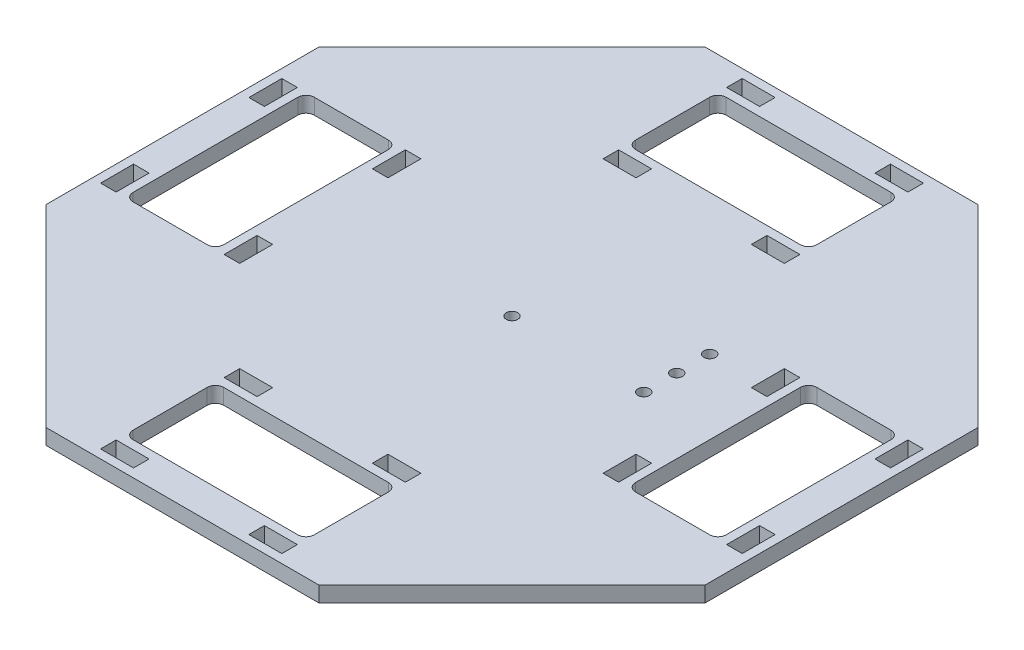
SolidWorks part; units mm, degrees
material "Custom Plastic"
ref_plane "Front Plane" through (0, 0, 0) normal (0, 0, 1) x (1, 0, 0)
ref_plane "Top Plane" through (0, 0, 0) normal (0, 1, 0) x (1, 0, 0)
ref_plane "Right Plane" through (0, 0, 0) normal (1, 0, 0) x (0, 0, -1)
ref_axis "Axis1" through (0, -0.2997, 0) along (0, 1, 0)
sketch "Base sketch" plane through (0, 0, 0) normal (0, 1, 0) x (1, 0, 0)
  line L1 (-127, 52.6051) -> (-127, -52.6051)
  line L2 (-127, -52.6051) -> (-52.6051, -127)
  line L3 (-52.6051, -127) -> (52.6051, -127)
  line L4 (52.6051, -127) -> (127, -52.6051)
  line L5 (127, -52.6051) -> (127, 52.6051)
  line L6 (127, 52.6051) -> (52.6051, 127)
  line L7 (52.6051, 127) -> (-52.6051, 127)
  line L8 (-52.6051, 127) -> (-127, 52.6051)
  circle A0 centre (0, 0) radius 127 construction
  dimension "D1" = 254
extrude "Base" add sketch "Base sketch" along normal blind 5.9944
sketch "Sketch3" plane through (0, 5.9944, 0) normal (0, 1, 0) x (1, 0, 0)
  line L0 (52.6051, 127) -> (-52.6051, 127) construction
  line L1 (-34.925, 114.3) -> (34.925, 114.3)
  line L2 (-34.925, 114.3) -> (-34.925, 79.375)
  line L4 (-34.925, 79.375) -> (34.925, 79.375)
  line L5 (34.925, 114.3) -> (34.925, 79.375)
  point P6 (0, 79.375)
  dimension "D1" = 69.85
  dimension "D2" = 34.925
  dimension "D3" = 12.7
extrude "Wheel cutout" cut sketch "Sketch3" against normal up to next
fillet "Wheel cutout fillets" radius 3.175 4 edges at (34.925, 2.9972, -114.3) (34.925, 2.9972, -79.375) (-34.925, 2.9972, -79.375) (-34.925, 2.9972, -114.3)
pattern_circular "Wheel cutout pattern" count 4 over 360 about axis through (0, -0.2997, 0) along (0, 1, 0) of "Wheel cutout", "Wheel cutout fillets"
sketch "Sketch4" plane through (0, 5.9944, 0) normal (0, 1, 0) x (1, 0, 0)
  line L0 (0, 0) -> (0, 127) construction
  line L1 (52.6051, 127) -> (-52.6051, 127) construction
  line L2 (34.925, 120.65) -> (-34.925, 120.65) construction
  line L3 (-34.925, 123.6472) -> (-22.225, 123.6472)
  line L4 (-34.925, 123.6472) -> (-34.925, 117.6528)
  line L5 (-34.925, 117.6528) -> (-22.225, 117.6528)
  line L6 (-22.225, 123.6472) -> (-22.225, 117.6528)
  line L7 (-34.925, 123.6472) -> (-22.225, 117.6528) construction
  line L8 (-34.925, 117.6528) -> (-22.225, 123.6472) construction
  line L10 (34.925, 117.6528) -> (22.225, 123.6472) construction
  line L11 (34.925, 123.6472) -> (22.225, 117.6528) construction
  line L12 (22.225, 123.6472) -> (22.225, 117.6528)
  line L13 (34.925, 117.6528) -> (22.225, 117.6528)
  line L14 (34.925, 123.6472) -> (34.925, 117.6528)
  line L15 (34.925, 123.6472) -> (22.225, 123.6472)
  line L16 (-34.925, 96.8375) -> (34.925, 96.8375) construction
  line L17 (-34.925, 111.125) -> (-34.925, 82.55) construction
  line L18 (34.925, 82.55) -> (34.925, 111.125) construction
  line L19 (34.925, 70.0278) -> (22.225, 76.0222) construction
  line L20 (34.925, 76.0222) -> (22.225, 70.0278) construction
  line L21 (-34.925, 76.0222) -> (-22.225, 70.0278) construction
  line L22 (-34.925, 70.0278) -> (-22.225, 76.0222) construction
  line L23 (34.925, 73.025) -> (-34.925, 73.025) construction
  line L24 (34.925, 70.0278) -> (22.225, 70.0278)
  line L25 (34.925, 70.0278) -> (34.925, 76.0222)
  line L26 (34.925, 76.0222) -> (22.225, 76.0222)
  line L27 (22.225, 70.0278) -> (22.225, 76.0222)
  line L28 (-22.225, 70.0278) -> (-22.225, 76.0222)
  line L29 (-34.925, 76.0222) -> (-22.225, 76.0222)
  line L30 (-34.925, 70.0278) -> (-34.925, 76.0222)
  line L31 (-34.925, 70.0278) -> (-22.225, 70.0278)
  point P5 (-28.575, 120.65)
  point P12 (0, 120.65)
  point P17 (28.575, 120.65)
  point P34 (28.575, 73.025)
  point P35 (-28.575, 73.025)
  dimension "D1" = 5.9944
  dimension "D2" = 12.7
  dimension "D3" = 69.85
  dimension "D4" = 6.35
extrude "Support cutouts" cut sketch "Sketch4" against normal up to next
pattern_circular "Support cutout pattern" count 4 over 360 about axis through (0, -0.2997, 0) along (0, 1, 0) of "Support cutouts"
sketch "Sketch6" plane through (0, 5.9944, 0) normal (0, 1, 0) x (1, 0, 0)
  line L0 (0, 0) -> (50.8, 0) construction
  line L1 (50.8, 0) -> (50.8, 25.4) construction
  point P3 (50.8, 12.7)
  dimension "D1" = 50.8
  dimension "D2" = 25.4
hole_wizard "#8 Clearance Hole1" positions "Sketch8" profile "Sketch7" hole size "#8" standard "ANSI Inch"
sketch "Sketch8" plane through (0, 5.9944, 0) normal (0, 1, 0) x (1, 0, 0)
  point P0 (0, 0)
  point P3 (50.8, 0)
  point P7 (50.8, 12.7)
  point P10 (50.8, 25.4)
sketch "Sketch7" plane through (0, 5.9944, 0) normal (1, 0, 0) x (0, 0, 1)
  line L0 (0, 0) -> (0, 5.9944)
  line L1 (0, 5.9944) -> (2.2479, 5.9944)
  line L2 (2.2479, 5.9944) -> (2.2479, 0)
  line L5 (2.2479, 0) -> (0, 0)
  line L10 (0, 5.9944) -> (-2.2479, 5.9944) construction
  line L11 (0, -6.35) -> (0, 107.95) construction
  dimension "Hole Dia." = 4.4958
  dimension "Hole Depth" = 5.9944
  dimension "Drill Angle" = 180
